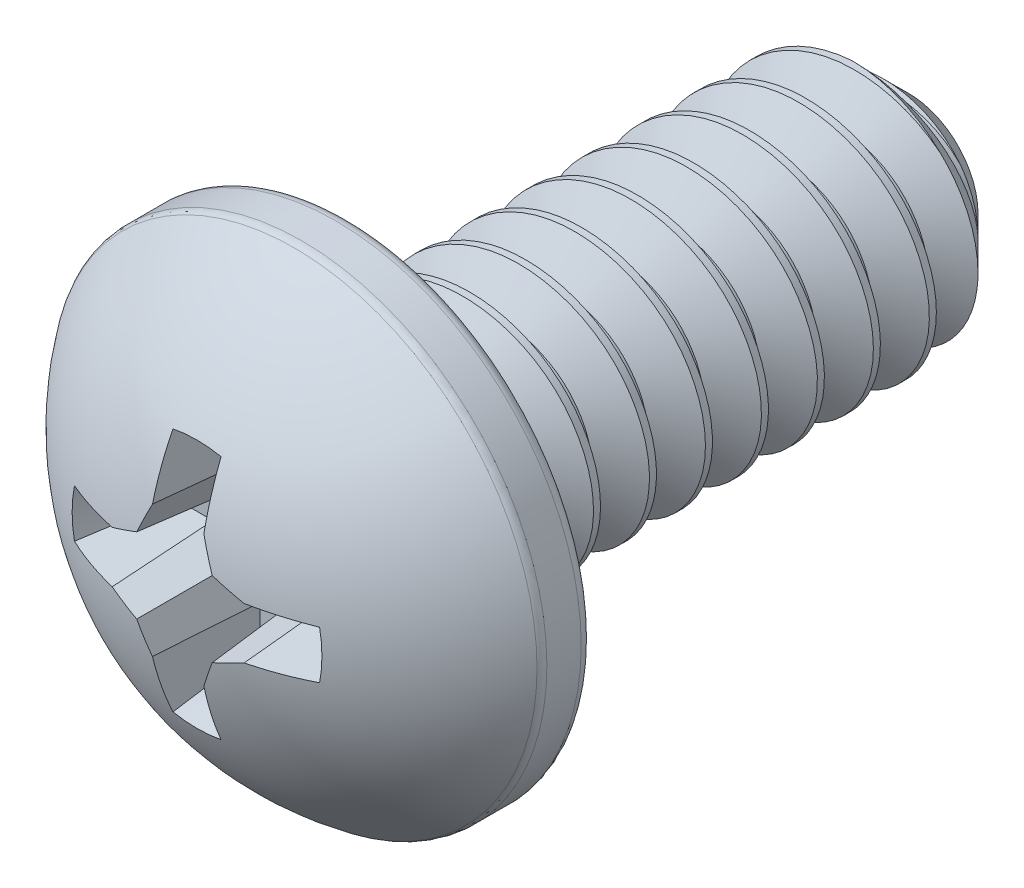
SolidWorks part; units mm, degrees
ref_plane "Front Plane" through (0, 0, 0) normal (0, 0, 1) x (1, 0, 0)
ref_plane "Top Plane" through (0, 0, 0) normal (0, 1, 0) x (1, 0, 0)
ref_plane "Right Plane" through (0, 0, 0) normal (1, 0, 0) x (0, 0, -1)
sketch "Sketch1" plane through (0, 0, 0) normal (1, 0, 0) x (0, 0, -1)
  line L0 (-4.191, 0) -> (4.191, 0) construction
  line L1 (4.191, 1.4224) -> (4.191, -1.4224) construction
  line L2 (-2.159, 2.7813) -> (-2.159, -2.7813) construction
  line L3 (4.1513, 1.4911) -> (4.7863, 1.4911) construction
  line L4 (4.1513, 1.4911) -> (4.4688, 0.9412) construction
  line L5 (4.4688, 0.9412) -> (4.7863, 1.4911) construction
  line L6 (4.4688, 1.4911) -> (4.4688, 1.4224) construction
  line L7 (4.4688, 0.9412) -> (4.4688, 1.01) construction
  line L8 (4.191, 1.4224) -> (4.7466, 1.4224) construction
  line L9 (4.1712, 1.4568) -> (4.7665, 1.4568) construction
  line L10 (4.4291, 1.01) -> (4.5085, 1.01) construction
  line L11 (-4.191, 1.5) -> (-4.191, -1.5) construction
  point P4 (0, 0)
  point P8 (4.191, 0)
  point P11 (-2.159, 0)
  point P16 (1.9685, -1.4224)
  point P20 (4.4688, 1.4224)
  point P23 (4.4688, 1.4568)
  point P26 (4.4688, 1.01)
  point P31 (-4.191, 0)
  dimension "D2" = 0.0794
  dimension "D1" = 2.2225
sketch "Sketch2" plane through (0, 0, 0) normal (1, 0, 0) x (0, 0, -1)
  line L0 (4.191, 0) -> (4.191, 0.7874)
  line L1 (4.191, 1.4224) -> (4.191, -1.4224) construction
  line L2 (4.191, 0.7874) -> (3.556, 1.4224)
  line L3 (3.556, 1.4224) -> (-2.159, 1.4224)
  line L4 (-2.159, 2.7813) -> (-2.159, -2.7813) construction
  line L5 (-2.159, 1.4224) -> (-2.159, 2.6362)
  line L6 (-2.3041, 2.7813) -> (-2.6934, 2.7813)
  line L7 (-4.191, 0) -> (4.191, 0) construction
  line L8 (-4.191, 0) -> (4.191, 0) construction
  line L9 (4.191, 0) -> (-4.191, 0)
  arc A0 (-2.7781, 2.7541) -> (-4.191, 0) centre (-0.8005, 0) ccw
  arc A1 (-2.6934, 2.7813) -> (-2.7781, 2.7541) centre (-2.6934, 2.6362) ccw
  arc A2 (-2.159, 2.6362) -> (-2.3041, 2.7813) centre (-2.3041, 2.6362) ccw
  point P20 (-2.7396, 2.7813)
  point P26 (-2.159, 2.7813)
  dimension "D4" = 0.1451
  dimension "D1" = 0.635
  dimension "D2" = 45
  dimension "D3" = 0.5806
revolve "Revolve1" add sketch "Sketch2" angle 360 about L8
ref_plane "Plane1" through (0, 0, 4.191) normal (0, 0, 1) x (1, 0, 0)
sketch "Sketch3" plane through (0, 0, 4.191) normal (0, 0, 1) x (1, 0, 0)
  line L0 (0.3, 0.75) -> (0.4318, 0.4318)
  line L1 (0.3, 1.4697) -> (0.3, 0.75)
  line L2 (0.75, 0.3) -> (1.4697, 0.3)
  line L3 (0.75, 0.3) -> (0.4318, 0.4318)
  line L4 (0.75, -0.3) -> (0.75, 0.3) construction
  line L5 (0.3, 0.75) -> (0.75, 0.3) construction
  line L6 (0.525, 0.525) -> (0, 0) construction
  line L7 (0, 0) -> (1.5, 0) construction
  line L8 (0, 0) -> (0, 1.5) construction
  line L9 (-0.75, 0.3) -> (-1.4697, 0.3)
  line L10 (-0.75, 0.3) -> (-0.4318, 0.4318)
  line L11 (-0.3, 0.75) -> (-0.4318, 0.4318)
  line L12 (-0.3, 1.4697) -> (-0.3, 0.75)
  line L13 (0.75, -0.3) -> (1.4697, -0.3)
  line L14 (0.3, -1.4697) -> (0.3, -0.75)
  line L15 (0.3, -0.75) -> (0.4318, -0.4318)
  line L16 (0.75, -0.3) -> (0.4318, -0.4318)
  line L17 (-0.75, -0.3) -> (-1.4697, -0.3)
  line L18 (-0.3, -1.4697) -> (-0.3, -0.75)
  line L19 (-0.3, -0.75) -> (-0.4318, -0.4318)
  line L20 (-0.75, -0.3) -> (-0.4318, -0.4318)
  circle A0 centre (0, 0) radius 1.5 construction
  arc A1 (-1.4697, 0.3) -> (-1.4697, -0.3) centre (0, 0) ccw
  arc A2 (-0.3, -1.4697) -> (0.3, -1.4697) centre (0, 0) ccw
  arc A3 (1.4697, 0.3) -> (1.4697, -0.3) centre (0, 0) cw
  arc A4 (-0.3, 1.4697) -> (0.3, 1.4697) centre (0, 0) cw
  point P11 (0.75, 0)
  dimension "D2" = 0.6
  dimension "D3" = 0.6
  dimension "D1" = 22.5
extrude "Cut-Extrude1" cut sketch "Sketch3" against normal blind 1.2192
draft "Draft1" type of draft neutral plane draft angle 15 neutral plane "Plane1" faces to draft 4 face at (1.4848, 0, 3.4065) face at (0, 1.4848, 3.4065) face at (0, -1.4848, 3.4065) face at (-1.4848, 0, 3.4065) neutral plane through (0, 0, 4.191) neutral plane normal (0, 0, 1) parameters "D1"=15
draft "Draft2" type of draft neutral plane draft angle 5 neutral plane "Plane1" faces to draft 16 face at (0.3, 0.9748, 3.3698) face at (0.9748, -0.3, 3.3698) face at (0.3, -0.9748, 3.3698) face at (-0.3, -0.9748, 3.3698) face at (-0.9748, -0.3, 3.3698) face at (-0.9748, 0.3, 3.3698) face at (-0.3, 0.9748, 3.3698) face at (0.9748, 0.3, 3.3698) face at (0.591, 0.3658, 3.5442) face at (0.3658, 0.591, 3.5442) face at (0.591, -0.3658, 3.5442) face at (0.3658, -0.591, 3.5442) face at (-0.3658, -0.591, 3.5442) face at (-0.591, -0.3658, 3.5442) face at (-0.591, 0.3658, 3.5442) face at (-0.3658, 0.591, 3.5442) neutral plane through (0, 0, 4.191) neutral plane normal (0, 0, 1) parameters "D1"=5
ref_axis "Center Axis1" through (0, 0, -87.463) along (0, 0, 1)
ref_plane "Contact Plane1" through (0, 0, -4.191) normal (0, 0, 1) x (1, 0, 0)
ref_plane "Contact Plane2" through (0, 0, 2.159) normal (0, 0, 1) x (1, 0, 0)
split "Split1" bodies to split 105 resulting bodies 106 107 split by face at (2.6362, 0, 2.159)
sketch "Sketch4" plane through (0, 0, -4.191) normal (0, 0, -1) x (-1, 0, 0)
  circle A0 centre (0, 0) radius 1.4224
curve "Helix/Spiral1" pitch 0.635 height 6.985 radius 1.4224 centre (0, 0, -4.191) axis (0, 0, 1) start towards (0, 1, 0)
sketch "Sketch5" plane through (0, 0, 0) normal (1, 0, 0) x (0, 0, -1)
  line L0 (4.1712, 1.4568) -> (4.4291, 1.01)
  line L1 (4.4291, 1.01) -> (4.5085, 1.01)
  line L2 (4.5085, 1.01) -> (4.7665, 1.4568)
  line L3 (4.7665, 1.4568) -> (4.1712, 1.4568)
sweep "Cut-Sweep1" cut profiles "Sketch5" path "Helix/Spiral1" align with end faces yes
sketch "Sketch6" plane through (0, 0, 2.159) normal (0, 0, -1) x (-1, 0, 0)
  circle A1 centre (0, 0) radius 1.4224
  circle A2 centre (0, 0) radius 1.4224
  dimension "D1" = 0
extrude "Boss-Extrude1" add sketch "Sketch6" along normal up to next (6.35 mm away) draft 20
equation "\"D2@Sketch1\" = \"Pitch@Sketch1\" / 8"
equation "\"D1@Sketch1\"=\"Pitch@Sketch1\"*3.50"
equation "\"D1@Sketch2\"=\"Pitch@Sketch1\""
equation "\"D3@Sketch2\"=\"Head Height@Sketch1\"/3.5"
equation "\"D4@Sketch2\"=\"D3@Sketch2\"/4"
equation "\"D3@Sketch3\"=\"D2@Sketch3\""
equation "\"D1@Cut-Extrude1\" = \"Head Height@Sketch1\" * .6"
equation "\"D2@Sketch3\"=\"Drive Size@Sketch1\"/5"
equation "\"D4@Helix/Spiral1\"=\"Pitch@sketch1\""
equation "\"D3@Helix/Spiral1\"=\"Length@sketch1\"+\"D4@Helix/Spiral1\""
